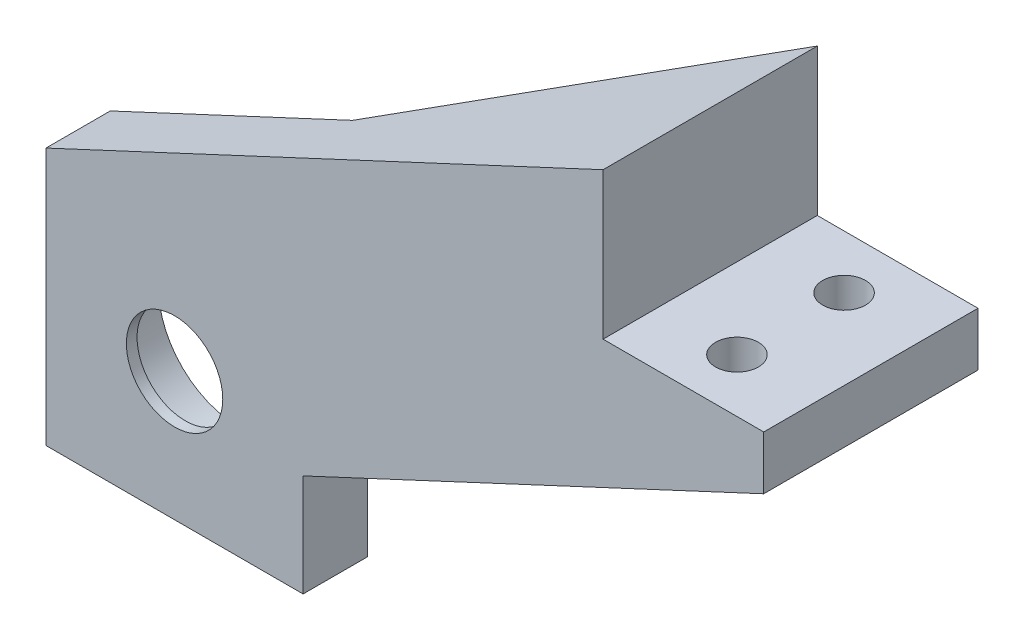
SolidWorks part; units mm, degrees
ref_plane "Front Plane" through (0, 0, 0) normal (0, 0, 1) x (1, 0, 0)
ref_plane "Top Plane" through (0, 0, 0) normal (0, 1, 0) x (1, 0, 0)
ref_plane "Right Plane" through (0, 0, 0) normal (1, 0, 0) x (0, 0, -1)
sketch "Sketch1" plane through (0, 0, 0) normal (0, 0, 1) x (1, 0, 0)
  circle A0 centre (0, 0) radius 7.5
  circle A1 centre (0, 0) radius 4.5
  circle A2 centre (0, 0) radius 10
  dimension "D1" = 15
  dimension "D2" = 20
  dimension "D3" = 9
extrude "Boss-Extrude1" add sketch "Sketch1" against normal up to surface (5 mm away) contours A2 A0 region at (-9.7172, 0, 0)
extrude "Boss-Extrude2" add sketch "Sketch1<3>" along normal blind 1 contours A0 A1 | A2 A0 region at (-7.2879, 0, 0) region at (-9.7172, 0, 0)
sketch "Sketch1<3>" plane through (0, 0, 0) normal (0, 0, 1) x (1, 0, 0) same geometry as "Sketch1"
sketch "Sketch2" plane through (0, 0, 1) normal (0, 0, 1) x (1, 0, 0)
  line L3 (55, 22.6) -> (40, 22.6)
  line L5 (-12, -0.9326) -> (-12, -12)
  line L6 (-12, -12) -> (12, -12)
  line L8 (40, 22.6) -> (40, 17.6)
  line L13 (40, 17.6) -> (55, 17.6)
  line L14 (55, 17.6) -> (55, 22.6)
  line L15 (-110, 22.6) -> (290, 22.6) construction
  line L16 (10.6203, 22.6) -> (-12, 12.052)
  line L17 (-12, -0.9326) -> (-12, 12.052)
  line L18 (40, 22.6) -> (10.6203, 22.6)
  line L19 (55, 17.6) -> (12, -2.4512)
  line L20 (12, -2.4512) -> (12, -12)
  line L21 (10.6203, 22.6) -> (40, 36.3)
  line L23 (34.0705, 37.9485) -> (-8.8692, 17.9254) construction
  line L24 (40, 22.6) -> (40, 34.3) construction
  line L25 (40, 36.3) -> (40, 22.6)
  circle A1 centre (0, 0) radius 10
  circle A2 centre (0, 0) radius 10 construction
  circle M4 centre (0, 0) radius 10
  dimension "D1" = 12
  dimension "D2" = 24
  dimension "D3" = 15
  dimension "D4" = 5
  dimension "D5" = 25
  dimension "D6" = 4
  dimension "D7" = 12
  dimension "D8" = 2
  dimension "D9" = 0
extrude "Boss-Extrude3" add sketch "Sketch2" against normal up to surface (6 mm away) contours L8 M4 | L6 L5 M4 | L8 | L25 L21 L18 region at (47.5, 20.1, 1) region at (16.0369, 9.9628, 1) region at (30.2068, 27.1667, 1) up to face at (-10, 0, -5)
sketch "Sketch3" plane through (0, 22.6, 0) normal (0, -1, 0) x (1, 0, 0)
  line L0 (40, -286) -> (40, 14) construction
  line L1 (55, -5) -> (40, -5)
  line L2 (55, -5) -> (55, -19)
  line L3 (55, -19) -> (40, -19)
  line L4 (40, -5) -> (40, -19)
  line L5 (55, -5) -> (40, -19) construction
  line L6 (55, -19) -> (40, -5) construction
  line L7 (55, 1) -> (12, 1) construction
  line L8 (40, -19) -> (10.6203, -5)
  line L9 (55, -5) -> (55, 1) construction
  line L10 (40, -5) -> (10.6203, -5)
  line L11 (40, -5) -> (-12, -5) construction
  point P4 (47.5, -12)
  dimension "D1" = 20
  dimension "D2" = 29.3797
extrude "Boss-Extrude7" add sketch "Sketch3" along normal up to surface (11.9946 mm away) contours L4 L10 L8 | L1 L4 L3 L2 region at (47.5, 22.6, -12) region at (30.2068, 22.6, -9.6667) up to face at (33.5, 7.5744, -2)
sketch "Sketch4" plane through (0, 22.6, 0) normal (0, -1, 0) x (1, 0, 0)
  line L1 (55, 1) -> (40, 1)
  line L2 (55, 1) -> (55, -19)
  line L3 (55, -19) -> (40, -19)
  line L4 (40, 1) -> (40, -19)
  line L5 (55, 1) -> (40, -19) construction
  line L6 (55, -19) -> (40, 1) construction
  line L7 (55, -19) -> (55, 1) construction
  line L8 (55, -9) -> (40, -9) construction
  line L9 (47.5, -9.9585) -> (44, -11.9793)
  line L10 (44, -11.9793) -> (44, -16.0207)
  line L11 (44, -16.0207) -> (47.5, -18.0415)
  line L12 (47.5, -18.0415) -> (51, -16.0207)
  line L13 (51, -16.0207) -> (51, -11.9793)
  line L14 (51, -11.9793) -> (47.5, -9.9585)
  line L21 (51, -6.0207) -> (47.5, -8.0415)
  line L22 (51, -1.9793) -> (51, -6.0207)
  line L23 (47.5, 0.0415) -> (51, -1.9793)
  line L24 (44, -1.9793) -> (47.5, 0.0415)
  line L25 (44, -6.0207) -> (44, -1.9793)
  line L26 (47.5, -8.0415) -> (44, -6.0207)
  line L27 (55, 1) -> (40, 1) construction
  circle A0 centre (47.5, -14) radius 3.5 construction
  circle A1 centre (47.5, -4) radius 3.5 construction
  circle A2 centre (47.5, -14) radius 2
  circle A3 centre (47.5, -4) radius 2
  point P4 (47.5, -9)
  point P28 (45.75, -10.9689)
  dimension "D3" = 4
  dimension "D1" = 7.5
  dimension "D2" = 7
  dimension "D4" = 5
  dimension "D5" = 15
  dimension "D6" = 20
extrude "Cut-Extrude4" cut sketch "Sketch4" along normal through all contours A2 | A3 region at (47.5, 22.6, -14) region at (47.5, 22.6, -4)
extrude "Cut-Extrude5" cut sketch "Sketch4<3>" along normal through all from offset 3 contours L26 L21 L22 L23 L24 L25 A3 | L13 L14 L9 L10 L11 L12 A2 region at (49.1965, 22.6, -11.0615) region at (49.1965, 22.6, -6.9385)
sketch "Sketch4<3>" plane through (0, 22.6, 0) normal (0, -1, 0) x (1, 0, 0) same geometry as "Sketch4"
extrude "Boss-Extrude8" add sketch "Sketch3<4>" against normal up to surface (13.7 mm away) contours L4 L10 L8 region at (30.2068, 22.6, -9.6667) up to face at (13.3241, 23.8608, -2.6)
sketch "Sketch3<4>" plane through (0, 22.6, 0) normal (0, -1, 0) x (1, 0, 0) same geometry as "Sketch3"
